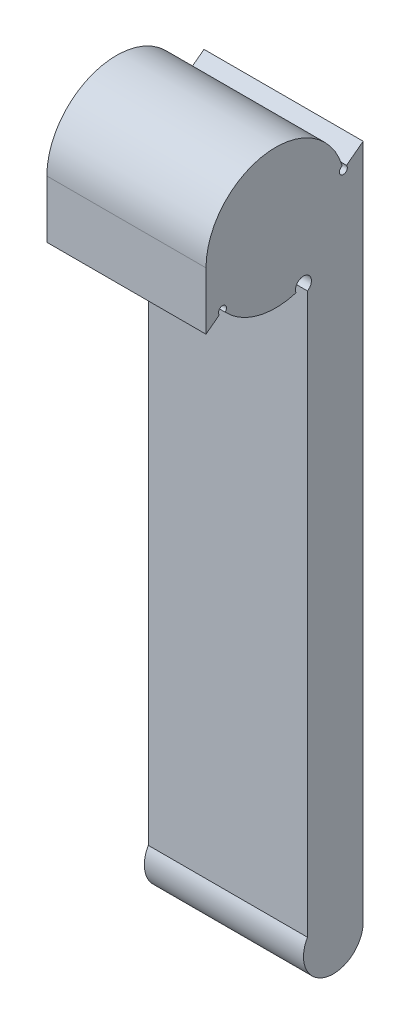
SolidWorks part; units mm, degrees
ref_plane "Front Plane" through (0, 0, 0) normal (1, 0, 0) x (0, 1, 0)
ref_plane "Top Plane" through (0, 0, 0) normal (0, 0, 1) x (0, 1, 0)
ref_plane "Right Plane" through (0, 0, 0) normal (0, 1, 0) x (-1, 0, 0)
sketch "Sketch1" plane through (0, 0, 0) normal (1, 0, 0) x (0, 1, 0)
  line L0 (24.6661, -15.2608) -> (21.7782, -15.2608)
  line L1 (21.7782, -15.2608) -> (22.4034, -16.0905)
  line L2 (22.4034, -16.0905) -> (24.6661, -15.2608)
  line L3 (24.6661, -18.7608) -> (21.1661, -18.7608) construction
  line L4 (25.4785, -22.1652) -> (26.2287, -23.1608)
  line L5 (26.2287, -23.1608) -> (-7.7713, -23.1608)
  line L7 (-7.7713, -20.1608) -> (21.4583, -20.1608)
  line L8 (25.4785, -22.1652) -> (21.4583, -20.1608)
  circle A0 centre (24.6661, -18.7608) radius 3.5
  circle A1 centre (24.6661, -18.7608) radius 0.2
  circle A2 centre (24.6661, -18.7608) radius 1.4
  arc A3 (-7.7713, -20.1608) -> (-7.7713, -23.1608) centre (-7.7713, -21.6608) ccw
  dimension "D1" = 7
  dimension "D2" = 0.4
  dimension "D3" = 2.8
  dimension "D4" = 53
  dimension "D5" = 3
  dimension "D6" = 34
extrude "Boss-Extrude1" add sketch "Sketch1" along normal blind 8 contours L7 A3 L5 L4 A0 | L8 A0 | A2 A0 L8 L2 | A0 L0 L1 | L2 A0 | A1 A2 | A1 region at (0, 22.7235, -15.5139) region at (0, 27.0714, -16.3554) region at (0, 23.5052, -15.5951) region at (0, 7.2829, -21.705) region at (0, 23.3212, -21.4581) region at (0, 24.6661, -18.7608) region at (0, 23.3057, -18.7608)
sketch "Sketch2" plane through (0, 0, 0) normal (-1, 0, 0) x (0, -1, 0)
  line L0 (-21.7782, -15.2608) -> (-22.4034, -16.0905) construction
  line L1 (-22.2546, -16.2241) -> (-22.2831, -15.9307)
  line L2 (-25.4785, -22.1652) -> (-26.2287, -23.1608) construction
  line L3 (-25.5989, -22.3249) -> (-25.6716, -22.1132)
  line L6 (7.7713, -20.1608) -> (-21.4583, -20.1608) construction
  line L7 (-21.1119, -20.3608) -> (7.0229, -20.3608)
  line L8 (-21.1119, -20.3608) -> (-21.4583, -20.1608)
  line L9 (-21.3195, -19.7856) -> (-21.3195, -20.1608)
  line L10 (-21.3195, -20.1608) -> (7.7713, -20.1608)
  arc A0 (-22.2831, -15.9307) -> (-22.2546, -16.2241) centre (-22.4034, -16.0905) ccw
  arc A1 (-21.4583, -20.1608) -> (-22.4034, -16.0905) centre (-24.6661, -18.7608) ccw construction
  arc A2 (-25.5989, -22.3249) -> (-25.6716, -22.1132) centre (-25.4785, -22.1652) ccw
  arc A3 (-24.6661, -15.2608) -> (-25.4785, -22.1652) centre (-24.6661, -18.7608) ccw construction
  arc A4 (-21.1119, -20.3608) -> (-21.3195, -19.7856) centre (-21.4583, -20.1608) cw
  arc A5 (7.7713, -20.1608) -> (7.0229, -20.3608) centre (7.7713, -21.6608) ccw
  arc A6 (7.7713, -23.1608) -> (7.7713, -20.1608) centre (7.7713, -21.6608) ccw construction
  point P29 (7.1908, -20.3608)
  line M11 (7.7713, -20.1608) -> (-21.4583, -20.1608)
  arc M12 (-21.4583, -20.1608) -> (-22.4034, -16.0905) centre (-24.6661, -18.7608) ccw
  line M13 (-22.4034, -16.0905) -> (-21.7782, -15.2608)
  arc M15 (-24.6661, -15.2608) -> (-25.4785, -22.1652) centre (-24.6661, -18.7608) ccw
  line M16 (-25.4785, -22.1652) -> (-26.2287, -23.1608)
  dimension "D1" = 0.2
  dimension "D2" = 0.2
  dimension "D3" = 0.4
  dimension "D4" = 0.2
extrude "Cut-Extrude1" cut sketch "Sketch2" against normal through all contours A0 M13 M12 | A4 L8 M12 | A2 M16 M15 | A5 L8 L7 M11 | L9 M12 M11 | L3 M16 M15 | L1 M12 M13 region at (0, 22.3136, -16.081) region at (0, 21.3644, -20.0396) region at (0, 21.542, -20.1903) region at (0, 22.4455, -16.0947) region at (0, 7.0095, -20.2602) region at (0, 25.451, -22.1556) region at (0, 25.5831, -22.2017)
equation "\"D1@Sketch1\"=\"stand_pivot_diameter@clock_monsieur.Assembly\""
equation "\"D2@Sketch1\"=\"stand_pivot_inset@clock_monsieur.Assembly\"*2"
equation "\"D3@Sketch1\"=\"stand_pivot_inset@clock_monsieur.Assembly\"*2+\"back_thickness@clock_monsieur.Assembly\"*2"
equation "\"D6@Sketch1\"=\"stand_length@clock_monsieur.Assembly\""
equation "\"D1@Boss-Extrude1\"=\"stand_width@clock_monsieur.Assembly\""
equation "\"D4@Sketch1\"=\"stand_max_angle@clock_monsieur.Assembly\""
equation "\"D2@Sketch2\"=\"D1@Sketch2\""
equation "\"D3@Sketch2\"=\"D1@Sketch2\"*2"
equation "\"D4@Sketch2\"=\"D1@Sketch2\""
